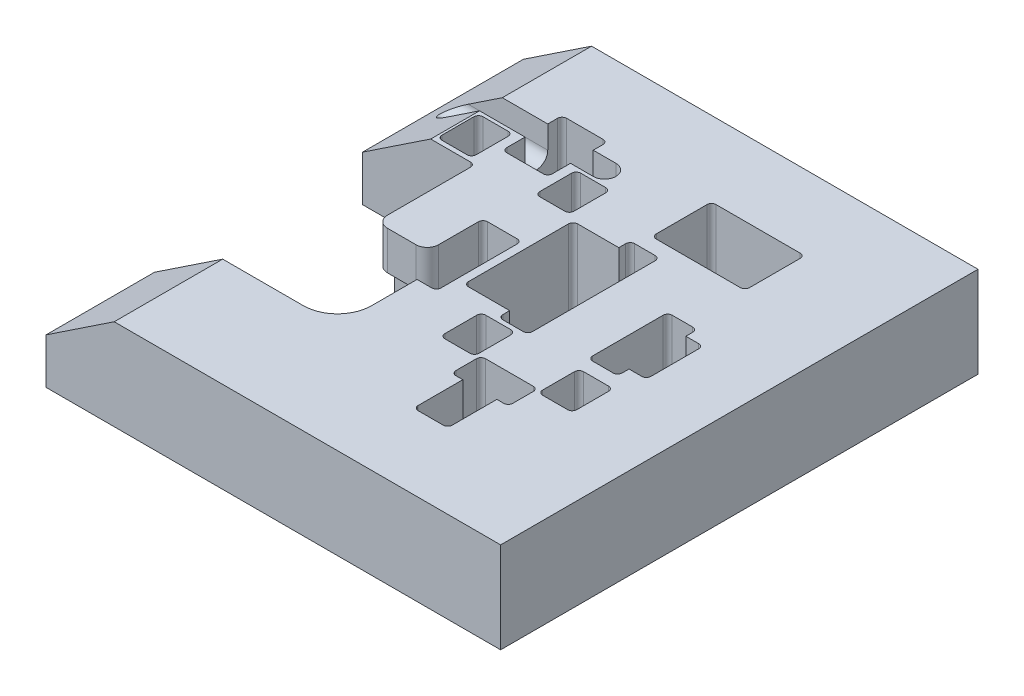
SolidWorks part; units mm, degrees
material "K110"
ref_plane "Front Plane" through (0, 0, 0) normal (0, 0, 1) x (1, 0, 0)
ref_plane "Top Plane" through (0, 0, 0) normal (0, 1, 0) x (1, 0, 0)
ref_plane "Right Plane" through (0, 0, 0) normal (1, 0, 0) x (0, 0, -1)
sketch "Sketch1" plane through (0, 0, 0) normal (0, 1, 0) x (1, 0, 0)
  line L1 (-100, -105) -> (100, -105)
  line L2 (-100, -105) -> (-100, 105)
  line L3 (-100, 105) -> (100, 105)
  line L4 (100, -105) -> (100, 105)
  line L5 (-100, -105) -> (100, 105) construction
  line L6 (-100, 105) -> (100, -105) construction
  point P0 (0, 0)
  dimension "D1" = 210
  dimension "D2" = 200
extrude "Boss-Extrude1" add sketch "Sketch1" along normal blind 40
sketch "Sketch2" plane through (0, 40, 0) normal (0, 1, 0) x (1, 0, 0)
  line L0 (17.25, 55.73) -> (55.25, 55.73) construction
  line L1 (15.75, 32.73) -> (15.75, -12.27) construction
  line L2 (58.25, 13.73) -> (58.25, -8.27) construction
  line L3 (30.25, -47.4) -> (42.25, -47.4) construction
  line L4 (17.25, 55.73) -> (55.25, 55.73)
  line L5 (15.75, 32.73) -> (15.75, -12.27)
  line L6 (58.25, 13.73) -> (58.25, -8.27)
  line L7 (30.25, -47.4) -> (42.25, -47.4)
sketch "Sketch3" plane through (0, 40, 0) normal (0, 1, 0) x (1, 0, 0)
  line L0 (30.25, -47.4) -> (42.25, -47.4) construction
  line L1 (28.75, -72.03) -> (43.75, -72.03)
  line L2 (28.75, -72.03) -> (28.75, -50.4)
  line L3 (23.75, -37.4) -> (48.75, -37.4)
  line L4 (43.75, -72.03) -> (43.75, -50.4)
  line L8 (36.25, -37.4) -> (36.25, -72.03) construction
  line L9 (36.25, 69.53) -> (36.25, -69.53) construction
  line L11 (43.75, -50.4) -> (48.75, -50.4)
  line L12 (48.75, -50.4) -> (48.75, -37.4)
  line L13 (28.75, -50.4) -> (23.75, -50.4)
  line L14 (23.75, -50.4) -> (23.75, -37.4)
  line L15 (66.38, -69.53) -> (-4.87, -69.53) construction
  dimension "D1" = 10
  dimension "D2" = 15
  dimension "D3" = 3
  dimension "D4" = 25
  dimension "D5" = 2.5
extrude "Cut-Extrude2" cut sketch "Sketch3" against normal up to next contours L3 L12 L11 L4 L1 L2 L13 L14
fillet "Fillet3" radius 2 6 edges at (43.75, 20, 72.03) (28.75, 20, 72.03) (48.75, 20, 50.4) (23.75, 20, 50.4) (48.75, 20, 37.4) (23.75, 20, 37.4)
sketch "Sketch4" plane through (0, 40, 0) normal (0, 1, 0) x (1, 0, 0)
  line L0 (48.25, -14.77) -> (61.25, -14.77)
  line L5 (61.25, -14.77) -> (61.25, -9.77)
  line L6 (64.38, 13.73) -> (58.25, 13.73) construction
  line L7 (66.38, 69.53) -> (66.38, -69.53) construction
  line L8 (66.38, 2.73) -> (51.7072, 2.73) construction
  line L9 (66.38, -6.27) -> (66.38, 11.73) construction
  line L10 (61.25, -9.77) -> (68.88, -9.77)
  line L11 (68.88, -9.77) -> (68.88, 15.23)
  line L13 (68.88, 15.23) -> (61.25, 15.23)
  line L14 (61.25, 15.23) -> (61.25, 20.23)
  line L15 (61.25, 20.23) -> (48.25, 20.23)
  line L16 (48.25, 20.23) -> (48.25, -14.77)
  line L17 (58.25, 13.73) -> (58.25, -8.27) construction
  dimension "D1" = 1.5
  dimension "D2" = 5
  dimension "D3" = 2.5
  dimension "D4" = 10
  dimension "D5" = 3
extrude "Cut-Extrude3" cut sketch "Sketch4" against normal up to next
fillet "Fillet4" radius 2 6 edges at (68.88, 20, 9.77) (68.88, 20, -15.23) (61.25, 20, -20.23) (48.25, 20, -20.23) (48.25, 20, 14.77) (61.25, 20, 14.77)
sketch "Sketch5" plane through (0, 40, 0) normal (0, 1, 0) x (1, 0, 0)
  line L0 (-7.37, -13.77) -> (12.75, -13.77)
  line L2 (12.75, -18.77) -> (25.75, -18.77)
  line L3 (25.75, -18.77) -> (25.75, 39.23)
  line L4 (25.75, 39.23) -> (12.75, 39.23)
  line L5 (12.75, 39.23) -> (12.75, 34.23)
  line L6 (12.75, 34.23) -> (-7.37, 34.23)
  line L7 (-7.37, 34.23) -> (-7.37, -13.77)
  line L8 (15.75, 32.73) -> (15.75, -12.27) construction
  line L9 (-4.87, 69.53) -> (-4.87, -69.53) construction
  line L10 (-4.87, 10.23) -> (25.75, 10.23) construction
  line L11 (-4.87, 26.73) -> (-4.87, -6.27) construction
  line L12 (12.75, -18.77) -> (12.75, -13.77)
  line L13 (1.13, -12.27) -> (15.75, -12.27) construction
  line L17 (-18, -8.27) -> (-18, 13.73) construction
  line L18 (-18, 2.73) -> (-15, 2.73) construction
  dimension "D1" = 3
  dimension "D2" = 10
  dimension "D3" = 2.5
  dimension "D4" = 1.5
  dimension "D5" = 5
extrude "Cut-Extrude4" cut sketch "Sketch5" against normal up to next
fillet "Fillet5" radius 2 6 edges at (25.75, 20, -39.23) (12.75, 20, 18.77) (25.75, 20, 18.77) (-7.37, 20, 13.77) (12.75, 20, -39.23) (-7.37, 20, -34.23)
sketch "Sketch6" plane through (0, 40, 0) normal (0, 1, 0) x (1, 0, 0)
  line L0 (15.75, 72.03) -> (15.75, 45.73)
  line L3 (15.75, 45.73) -> (56.75, 45.73)
  line L6 (56.75, 45.73) -> (56.75, 72.03)
  line L7 (56.75, 72.03) -> (15.75, 72.03)
  line L8 (36.25, 69.53) -> (36.25, 45.73) construction
  line L9 (36.25, 69.53) -> (36.25, -69.53) construction
  line L10 (66.38, 69.53) -> (-4.87, 69.53) construction
  line L12 (17.25, 55.73) -> (55.25, 55.73) construction
  dimension "D1" = 2.5
  dimension "D2" = 41
  dimension "D5" = 10
extrude "Cut-Extrude5" cut sketch "Sketch6" against normal up to next
fillet "Fillet6" radius 2 4 edges at (15.75, 20, -72.03) (56.75, 20, -72.03) (15.75, 20, -45.73) (56.75, 20, -45.73)
sketch "Sketch7" plane through (0, 40, 0) normal (0, 1, 0) x (1, 0, 0)
  line L0 (57.75, -29.77) -> (57.75, -32.27) construction
  line L3 (60.25, -29.77) -> (55.25, -29.77) construction
  line L4 (60.25, -27.27) -> (60.25, -32.27) construction
  line L5 (55.25, -11.27) -> (55.25, -38.4) construction
  line L7 (63.25, -20.77) -> (52.25, -20.77)
  line L8 (65.25, -22.77) -> (65.25, -36.77)
  line L9 (63.25, -38.77) -> (52.25, -38.77)
  line L10 (50.25, -22.77) -> (50.25, -36.77)
  arc A2 (52.25, -38.77) -> (50.25, -36.77) centre (52.25, -36.77) cw
  arc A3 (65.25, -36.77) -> (63.25, -38.77) centre (63.25, -36.77) cw
  arc A4 (63.25, -20.77) -> (65.25, -22.77) centre (63.25, -22.77) cw
  arc A5 (52.25, -20.77) -> (50.25, -22.77) centre (52.25, -22.77) ccw
  point P14 (50.25, -38.77)
  point P17 (65.25, -38.77)
  point P20 (65.25, -20.77)
  dimension "D4" = 2
  dimension "D1" = 2.5
  dimension "D2" = 18
  dimension "D3" = 15
  dimension "D5" = 9
extrude "Cut-Extrude6" cut sketch "Sketch7" against normal up to next
sketch "Sketch8" plane through (0, 40, 0) normal (0, 1, 0) x (1, 0, 0)
  line L0 (12.25, -29.77) -> (17.25, -29.77) construction
  line L3 (12.25, -32.27) -> (12.25, -27.27) construction
  line L4 (63.25, -20.77) -> (52.25, -20.77) construction
  line L7 (17.25, -38.4) -> (17.25, -13.77) construction
  line L8 (14.75, -29.77) -> (14.75, -32.27) construction
  line L9 (52.25, -38.77) -> (63.25, -38.77) construction
  line L10 (9.25, -20.77) -> (20.25, -20.77)
  line L11 (7.25, -22.77) -> (7.25, -36.77)
  line L12 (9.25, -38.77) -> (20.25, -38.77)
  line L13 (22.25, -22.77) -> (22.25, -36.77)
  arc A2 (7.25, -36.77) -> (9.25, -38.77) centre (9.25, -36.77) ccw
  arc A3 (20.25, -38.77) -> (22.25, -36.77) centre (20.25, -36.77) ccw
  arc A4 (20.25, -20.77) -> (22.25, -22.77) centre (20.25, -22.77) cw
  arc A5 (9.25, -20.77) -> (7.25, -22.77) centre (9.25, -22.77) ccw
  dimension "D1" = 2.5
  dimension "D2" = 2
extrude "Cut-Extrude7" cut sketch "Sketch8" against normal up to next
sketch "Sketch21" plane through (0, 40, 0) normal (0, 1, 0) x (1, 0, 0)
  line L0 (-21, 55.73) -> (-21, 16.73) construction
  line L3 (-24, 54.23) -> (-13, 54.23)
  line L4 (-26, 52.23) -> (-26, 38.23)
  line L5 (-24, 36.23) -> (-13, 36.23)
  line L6 (-11, 52.23) -> (-11, 38.23)
  line L7 (-21, 55.73) -> (-59, 55.73) construction
  line L9 (-16, 45.23) -> (-21, 45.23) construction
  line L10 (-18.5, 45.23) -> (-18.5, 54.23) construction
  line L11 (-40, 55.73) -> (-40, 36.23) construction
  line L12 (-16, 42.73) -> (-16, 47.73) construction
  line L16 (-69, 52.23) -> (-69, 38.23)
  line L17 (-56, 36.23) -> (-67, 36.23)
  line L18 (-54, 52.23) -> (-54, 38.23)
  line L19 (-56, 54.23) -> (-67, 54.23)
  arc A2 (-26, 38.23) -> (-24, 36.23) centre (-24, 38.23) ccw
  arc A3 (-13, 36.23) -> (-11, 38.23) centre (-13, 38.23) ccw
  arc A4 (-13, 54.23) -> (-11, 52.23) centre (-13, 52.23) cw
  arc A5 (-24, 54.23) -> (-26, 52.23) centre (-24, 52.23) ccw
  arc A6 (-56, 54.23) -> (-54, 52.23) centre (-56, 52.23) cw
  arc A7 (-67, 54.23) -> (-69, 52.23) centre (-67, 52.23) ccw
  arc A8 (-67, 36.23) -> (-69, 38.23) centre (-67, 38.23) cw
  arc A9 (-54, 38.23) -> (-56, 36.23) centre (-56, 38.23) cw
  point P12 (0, 0)
  point P17 (0, 0)
  point P23 (0, 0)
  point P24 (0, 0)
  point P25 (0, 0)
  point P28 (0, 0)
  dimension "D4" = 15
  dimension "D2" = 2
  dimension "D1" = 2.5
  dimension "D3" = 18
extrude "Cut-Extrude12" cut sketch "Sketch21" against normal up to next
sketch "Sketch22" plane through (0, 40, 0) normal (0, 1, 0) x (1, 0, 0)
  line L0 (-100, 105) -> (-100, -105) construction
  line L1 (-100, 55.73) -> (-15, 55.73)
  line L2 (-100, 55.73) -> (-100, 65.726)
  line L3 (-100, 65.726) -> (-15, 65.726)
  line L4 (-15, 55.73) -> (-15, 65.726)
  line L5 (-21, 55.73) -> (-59, 55.73) construction
  line L6 (-59, 63.776) -> (-21, 63.776) construction
  line L7 (-21, 55.73) -> (-21, 61.5256) construction
  line L8 (-15, 60.728) -> (-100, 60.728) construction
  dimension "D1" = 1.95
  dimension "D2" = 6
ref_plane "Plane1" through (0, 0, -60.728) normal (0, 0, -1) x (-1, 0, 0)
sketch "Sketch24" plane through (0, 0, -60.728) normal (0, 0, -1) x (-1, 0, 0)
  line L0 (15, 40) -> (15, 35)
  line L1 (15, 40) -> (100, 40) construction
  line L2 (25, 25) -> (100, 25)
  line L3 (100, 40) -> (100, 0) construction
  line L4 (15, 40) -> (100, 40)
  line L5 (100, 40) -> (100, 25)
  arc A0 (15, 35) -> (25, 25) centre (25, 35) ccw
  dimension "D2" = 10
  dimension "D1" = 15
extrude "Cut-Extrude15" cut sketch "Sketch24" against normal mid plane 10
fillet "Fillet9" 2 edges at (-62.5, 25, -55.728) (-62.5, 25, -65.728) type full round first side face at (-50.5858, 32.5858, -55.728) second side face at (-50.5858, 32.5858, -65.728) middle face at (-62.5, 25, -60.728)
sketch "Sketch23" plane through (0, 40, 0) normal (0, 1, 0) x (1, 0, 0)
  line L0 (-40, 55.73) -> (-40, 45.73) construction
  line L1 (-48, 72.03) -> (-32, 72.03)
  line L2 (-50, 70.03) -> (-50, 47.73)
  line L3 (-48, 45.73) -> (-32, 45.73)
  line L4 (-30, 70.03) -> (-30, 47.73)
  line L5 (-21, 55.73) -> (-59, 55.73) construction
  line L6 (17.75, 45.73) -> (54.75, 45.73) construction
  line L7 (54.75, 72.03) -> (17.75, 72.03) construction
  arc A0 (-50, 47.73) -> (-48, 45.73) centre (-48, 47.73) ccw
  arc A1 (-48, 72.03) -> (-50, 70.03) centre (-48, 70.03) ccw
  arc A2 (-32, 72.03) -> (-30, 70.03) centre (-32, 70.03) cw
  arc A3 (-32, 45.73) -> (-30, 47.73) centre (-32, 47.73) ccw
  point P14 (-50, 45.73)
  point P21 (-30, 45.73)
  dimension "D2" = 2
  dimension "D1" = 20
extrude "Cut-Extrude14" cut sketch "Sketch23" against normal up to next
sketch "Sketch26" plane through (0, 40, 0) normal (0, 1, 0) x (1, 0, 0)
  line L0 (-100, 55.728) -> (-100, -105) construction
  line L1 (-100, 34.23) -> (-50.5, 34.23)
  line L2 (-100, 34.23) -> (-100, -57.27)
  line L3 (-100, -57.27) -> (-19.5, -57.27)
  line L4 (-19.5, -22.27) -> (-19.5, -57.27)
  line L5 (-60.5, 32.73) -> (-66.5, 32.73) construction
  line L6 (-50.5, 34.23) -> (-50.5, -9.27)
  line L7 (-50.5, -9.27) -> (-28, -9.27)
  line L8 (-59, -19.27) -> (-21, -19.27) construction
  line L9 (-21, -11.27) -> (-21, -19.27) construction
  line L10 (-28, -9.27) -> (-28, 15.23)
  line L11 (-60.5, -12.27) -> (-60.5, 32.73) construction
  line L12 (-19.5, -22.27) -> (-11, -22.27)
  line L13 (-11, -22.27) -> (-11, 15.23)
  line L14 (-28, 15.23) -> (-11, 15.23)
  line L15 (-18, -8.27) -> (-18, 13.73) construction
  line L16 (-12, 13.73) -> (-18, 13.73) construction
  dimension "D1" = 1.5
  dimension "D2" = 10
  dimension "D3" = 1.5
  dimension "D4" = 35
  dimension "D5" = 10
  dimension "D6" = 1.5
  dimension "D7" = 3
  dimension "D8" = 10
  dimension "D9" = 7
extrude "Cut-Extrude16" cut sketch "Sketch26" against normal up to next contours L1 L6 L7 L10 L14 L13 L12 L4 L3 L2
fillet "Fillet10" radius 2 4 edges at (-11, 20, 22.27) (-50.5, 20, -34.23) (-11, 20, -15.23) (-28, 20, -15.23)
sketch "Sketch27" plane through (-50.5, 0, 0) normal (-1, 0, 0) x (0, 0, 1)
  line L0 (-32.23, 0) -> (9.27, 0) construction
  line L1 (1.27, 0) -> (9.27, 0)
  line L2 (1.27, 0) -> (1.27, 23)
  line L3 (1.27, 23) -> (9.27, 23)
  line L4 (9.27, 0) -> (9.27, 23)
  line L5 (9.27, 23) -> (9.27, 0) construction
  dimension "D1" = 23
  dimension "D2" = 8
extrude "Cut-Extrude17" cut sketch "Sketch27" against normal blind 18.5 contours L4 L3 L2 L1
fillet "Fillet11" radius 3 3 edges at (-32, 23, 5.27) (-41.25, 23, 1.27) (-32, 11.5, 1.27)
fillet "Fillet12" radius 15 1 edges at (-19.5, 20, 57.27)
fillet "Fillet13" radius 5 2 edges at (-50.5, 31.5, 9.27) (-28, 20, 9.27)
chamfer "Chamfer1" distance 20 distance2 30 2 edges at (-100, 40, -44.979) (-100, 40, 81.135) first distance on face at (-100, 26.875, -65.1715) first distance on face at (-100, 20, 81.135)
